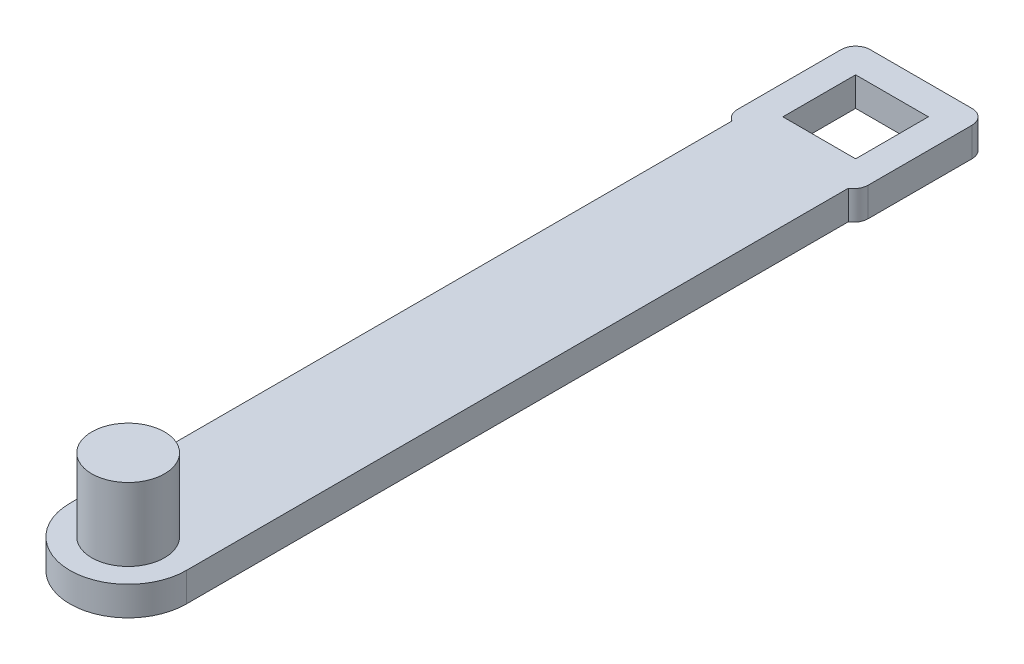
SolidWorks part; units mm, degrees
ref_plane "Front Plane" through (0, 0, 0) normal (0, 0, 1) x (1, 0, 0)
ref_plane "Top Plane" through (0, 0, 0) normal (0, 1, 0) x (1, 0, 0)
ref_plane "Right Plane" through (0, 0, 0) normal (1, 0, 0) x (0, 0, -1)
sketch "Sketch1" plane through (0, 0, 0) normal (0, 1, 0) x (1, 0, 0)
  line L0 (-4.6553, 12.0447) -> (-4.6553, 7.0447)
  line L2 (-6.1553, 5.0447) -> (-6.1553, -40.4553)
  line L4 (1.8447, 5.0447) -> (1.8447, -40.4553)
  line L5 (-6.6553, 14.0447) -> (2.3447, 14.0447)
  line L6 (-6.6553, 14.0447) -> (-6.6553, 5.0447)
  line L7 (-6.6553, 5.0447) -> (-6.1553, 5.0447)
  line L8 (2.3447, 14.0447) -> (2.3447, 5.0447)
  line L9 (-4.6553, 7.0447) -> (0.3447, 7.0447)
  line L10 (0.3447, 12.0447) -> (0.3447, 7.0447)
  line L11 (-4.6553, 12.0447) -> (0.3447, 12.0447)
  line L14 (-6.6553, 5.0447) -> (2.3447, 5.0447) construction
  arc A0 (-6.1553, -40.4553) -> (1.8447, -40.4553) centre (-2.1553, -40.4553) ccw
  dimension "D1" = 9
  dimension "D2" = 9
  dimension "D4" = 8
  dimension "D5" = 0.5
  dimension "D6" = 45.5
  dimension "D3" = 2
extrude "Boss-Extrude1" add sketch "Sketch1" along normal mid plane 2 contours L14 L2 A0 L4 | L7 L14 L8 L5 L6 L0 L11 L10 L9 region at (-2.1553, 0, 19.2843) region at (-6.4053, 0, -5.172)
fillet "Fillet1" radius 1 4 edges at (2.3447, 0, -5.0447) (2.3447, 0, -14.0447) (-6.6553, 0, -5.0447) (-6.6553, 0, -14.0447)
sketch "Sketch2" plane through (0, 1, 0) normal (0, 1, 0) x (1, 0, 0)
  circle A0 centre (-2.1553, -40.4553) radius 2.5
  arc A1 (-6.1553, -40.4553) -> (1.8447, -40.4553) centre (-2.1553, -40.4553) ccw construction
  dimension "D1" = 5
extrude "Boss-Extrude2" add sketch "Sketch2" along normal blind 5
